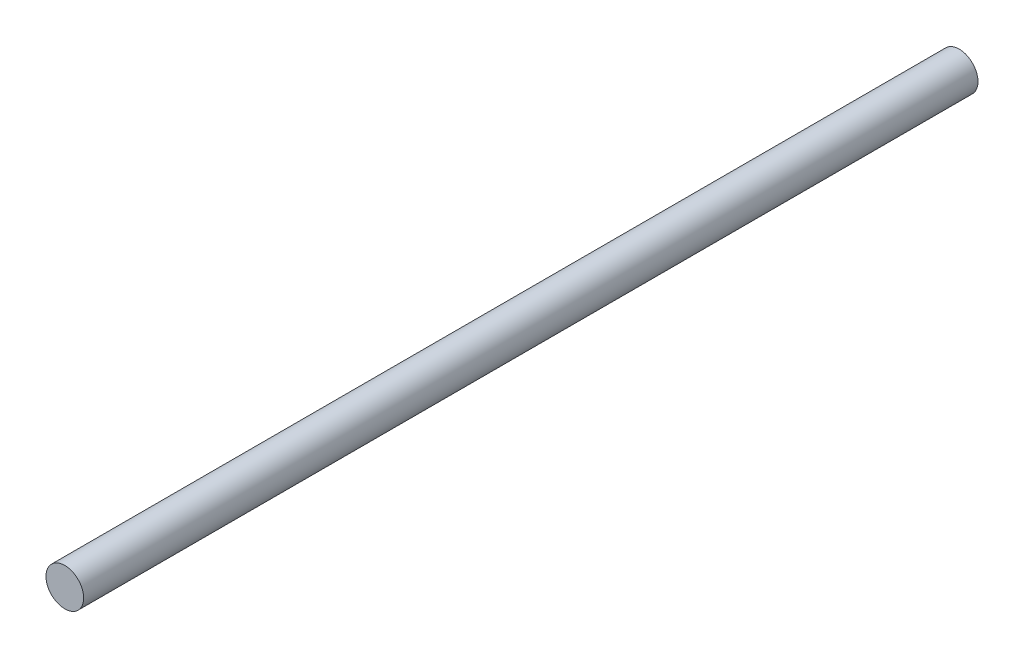
SolidWorks part; units mm, degrees
ref_plane "Front Plane" through (0, 0, 0) normal (0, 0, 1) x (1, 0, 0)
ref_plane "Top Plane" through (0, 0, 0) normal (0, 1, 0) x (1, 0, 0)
ref_plane "Right Plane" through (0, 0, 0) normal (1, 0, 0) x (0, 0, -1)
sketch "Sketch1" plane through (0, 0, 0) normal (0, 0, 1) x (1, 0, 0)
  circle A0 centre (0, 0) radius 4
extrude "Boss-Extrude1" add sketch "Sketch1" along normal blind 190
